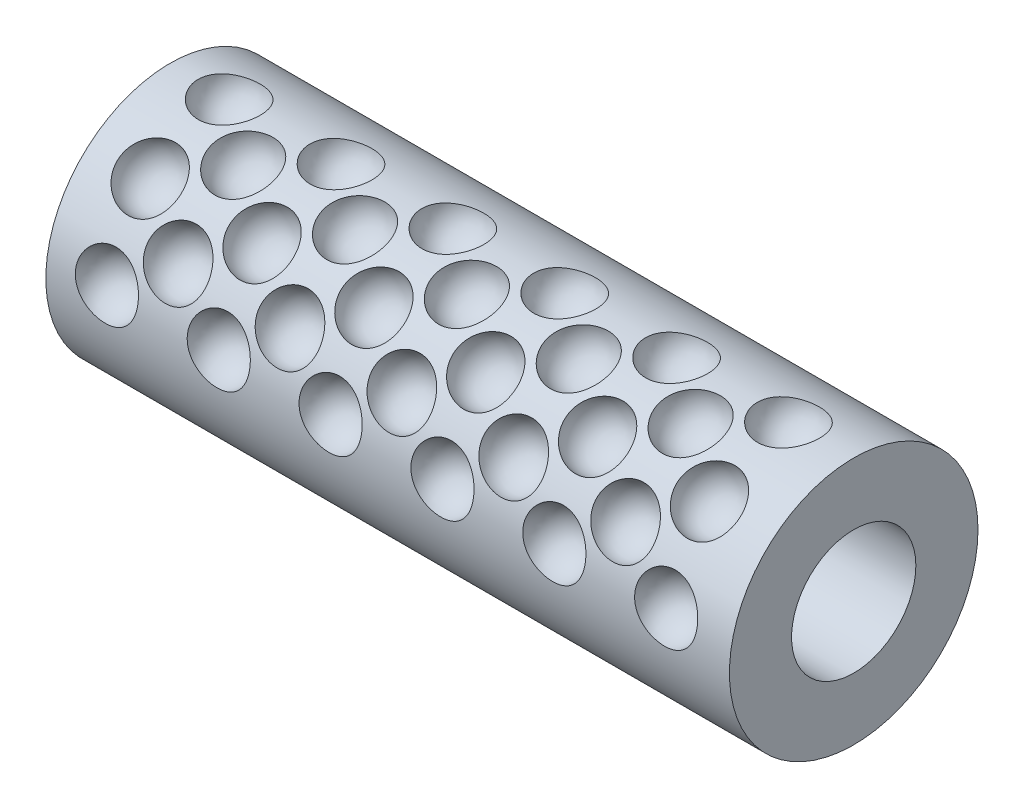
SolidWorks part; units mm, degrees
ref_plane "Front Plane" through (0, 0, 0) normal (0, 0, 1) x (1, 0, 0)
ref_plane "Top Plane" through (0, 0, 0) normal (0, 1, 0) x (1, 0, 0)
ref_plane "Right Plane" through (0, 0, 0) normal (1, 0, 0) x (0, 0, -1)
sketch "Sketch1" plane through (0, 0, 0) normal (1, 0, 0) x (0, 0, -1)
  circle A0 centre (0, 0) radius 5.08
  dimension "D1" = 10.16
extrude "Boss-Extrude1" add sketch "Sketch1" along normal mid plane 27.94
sketch "Sketch4" plane through (13.97, 0, 0) normal (1, 0, 0) x (0, 0, -1)
  circle A0 centre (0, 0) radius 2.54
  dimension "D1" = 5.08
ref_plane "Plane1" through (-11.557, 0, 0) normal (-1, 0, 0) x (0, 0, 1)
sketch "Sketch7" plane through (-11.557, 0, 0) normal (-1, 0, 0) x (0, 0, 1)
  line L0 (0, 0) -> (0, 6.7687) construction
  line L1 (0, 5.08) -> (0, 3.81)
  line L3 (-1.27, 5.08) -> (-1.27, 5.4418)
  line L4 (-1.27, 5.4418) -> (0, 5.4418)
  line L5 (0, 5.4418) -> (0, 5.08)
  circle A0 centre (0, 0) radius 5.08 construction
  arc A1 (-1.27, 5.08) -> (0, 3.81) centre (0, 5.08) ccw
  dimension "D1" = 1.27
revolve "Primary Dimple" cut sketch "Sketch7" angle 360 about L0
pattern_linear "LPattern1" count 6 spacing 4.572 along (1, 0, 0) of "Primary Dimple"
pattern_circular "CirPattern1" count 3 every 40 about axis through (0, 0, 0) along (1, 0, 0) of "LPattern1", "Primary Dimple"
sketch "Sketch9" plane through (0, 0, 0) normal (0, 0, 1) x (1, 0, 0)
  line L0 (-50.8865, 0) -> (50.8865, 0) construction
  point P4 (0, 0)
ref_plane "Plane2" through (0, 0, 0) normal (0, 0.7071, 0.7071) x (1, 0, 0)
mirror "Mirror3" about plane through (0, 0, 0) normal (0, 0.7071, 0.7071) of "CirPattern1", "Primary Dimple", "LPattern1"
sketch "Sketch10" plane through (-13.97, 0, 0) normal (-1, 0, 0) x (0, 0, 1)
  line L0 (-3.81, 3.3601) -> (3.81, 3.3601) construction
  circle A0 centre (0, 0) radius 5.08 construction
  dimension "D1" = 7.62
  dimension "D2" = 3.3601
sketch "Sketch12" plane through (-11.557, 0, 0) normal (-1, 0, 0) x (0, 0, 1)
  line L0 (0, 0) -> (3.2654, 3.8915) construction
  line L1 (0, 0) -> (0, 6.7687) construction
  line L2 (0, 0) -> (2.4805, 6.8151) construction
  line L3 (0.7786, 2.1391) -> (3.0936, 8.4996) construction
  line L4 (1.7375, 4.7736) -> (1.3031, 3.5802)
  line L5 (0.5441, 5.208) -> (0.6657, 5.5422)
  line L6 (0.6657, 5.5422) -> (1.8591, 5.1078)
  line L7 (1.8591, 5.1078) -> (1.7375, 4.7736)
  circle A0 centre (0, 0) radius 5.08 construction
  arc A1 (0.5441, 5.208) -> (1.3031, 3.5802) centre (1.7375, 4.7736) ccw
  dimension "D4" = 1.27
  dimension "D1" = 40
  dimension "D2" = 20
  dimension "D3" = 0.3556
ref_plane "Plane3" through (-9.271, 0, 0) normal (-1, 0, 0) x (0, 0, 1)
sketch "Sketch13" plane through (-9.271, 0, 0) normal (-1, 0, 0) x (0, 0, 1)
  line L0 (0, 0) -> (3.2654, 3.8915) construction
  line L1 (0, 0) -> (2.4805, 6.8151) construction
  line L2 (0.7786, 2.1391) -> (3.0936, 8.4996) construction
  line L3 (1.7375, 4.7736) -> (1.3031, 3.5802)
  line L4 (0.5441, 5.208) -> (0.6657, 5.5422)
  line L5 (0.6657, 5.5422) -> (1.8591, 5.1078)
  line L6 (1.8591, 5.1078) -> (1.7375, 4.7736)
  arc A0 (0.5441, 5.208) -> (1.3031, 3.5802) centre (1.7375, 4.7736) ccw
revolve "Secondary Dimple" cut sketch "Sketch13" angle 360 about L2
pattern_linear "LPattern3" count 5 spacing 4.572 along (1, 0, 0) of "Secondary Dimple"
pattern_circular "CirPattern2" count 2 every 40 about axis through (-13.97, 0, 0) along (1, 0, 0) of "LPattern3", "Secondary Dimple"
mirror "Mirror4" about plane through (0, 0, 0) normal (0, 0.7071, 0.7071) of "CirPattern2", "LPattern3", "Secondary Dimple"
extrude "Cut-Extrude1" cut sketch "Sketch4" against normal through all
